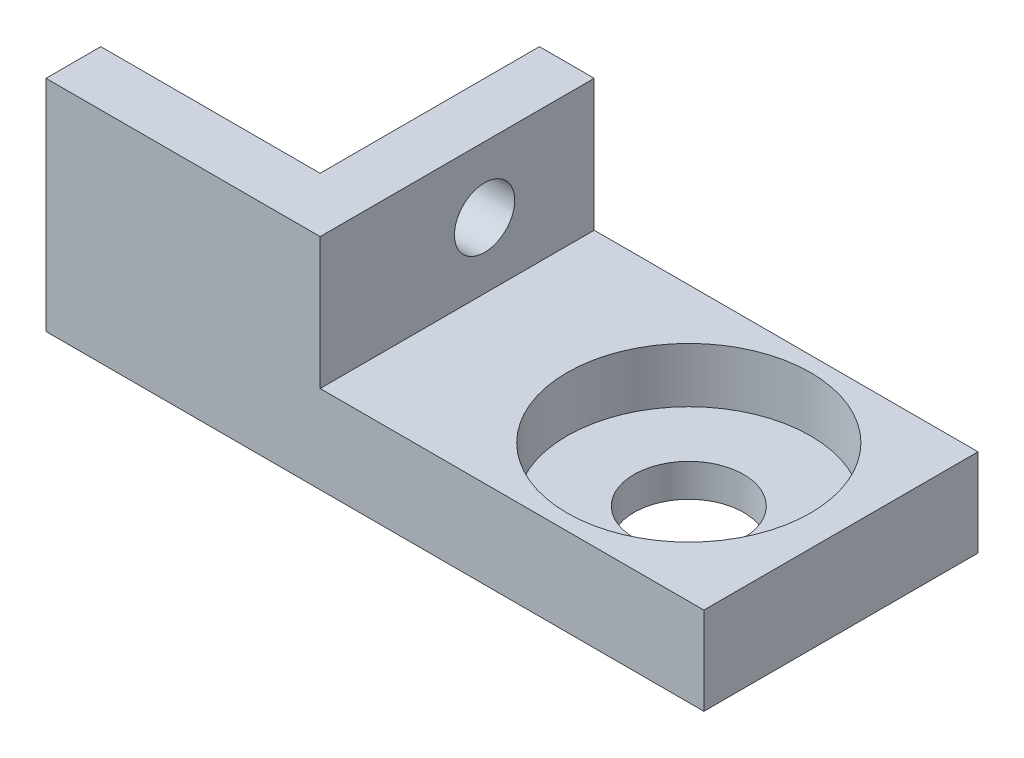
SolidWorks part; units mm, degrees
ref_plane "Front Plane" through (0, 0, 0) normal (0, 0, 1) x (1, 0, 0)
ref_plane "Top Plane" through (0, 0, 0) normal (0, 1, 0) x (1, 0, 0)
ref_plane "Right Plane" through (0, 0, 0) normal (1, 0, 0) x (0, 0, -1)
sketch "Sketch1" plane through (0, 0, 0) normal (0, 1, 0) x (1, 0, 0)
  line L1 (0, 0) -> (60, 0)
  line L2 (0, 0) -> (0, 5)
  line L3 (20, 25) -> (60, 25)
  line L4 (60, 0) -> (60, 25)
  line L7 (0, 5) -> (20, 5)
  line L8 (20, 25) -> (20, 5)
  dimension "D2" = 60
extrude "Boss-Extrude1" add sketch "Sketch1" along normal blind 20
sketch "Sketch2" plane through (0, 20, 0) normal (0, 1, 0) x (1, 0, 0)
  line L0 (20, 25) -> (20, 5) construction
  line L1 (60, 25) -> (25, 25)
  line L2 (60, 25) -> (60, 0)
  line L3 (60, 0) -> (25, 0)
  line L4 (25, 25) -> (25, 0)
  dimension "D1" = 25
  dimension "D2" = 5
extrude "Cut-Extrude1" cut sketch "Sketch2" against normal blind 12
sketch "Sketch3" plane through (0, 8, 0) normal (0, 1, 0) x (1, 0, 0)
  line L0 (25, 25) -> (25, 0) construction
  circle A0 centre (46.1, 12.5258) radius 11.1
  dimension "D1" = 22.2
  dimension "D2" = 10
extrude "Cut-Extrude2" cut sketch "Sketch3" against normal blind 5
sketch "Sketch4" plane through (0, 3, 0) normal (0, 1, 0) x (1, 0, 0)
  circle A0 centre (46.1, 12.5258) radius 5
  dimension "D1" = 10
extrude "Cut-Extrude3" cut sketch "Sketch4" against normal through all
sketch "Sketch5" plane through (25, 0, 0) normal (1, 0, 0) x (0, 0, -1)
  line L0 (25, 20) -> (0, 20) construction
  line L2 (5, 20) -> (5, 0) construction
  circle A0 centre (15, 14) radius 2.75
  point P4 (12.5, 20)
  dimension "D1" = 5.5
  dimension "D2" = 6
  dimension "D3" = 10
extrude "Cut-Extrude4" cut sketch "Sketch5" against normal through all
